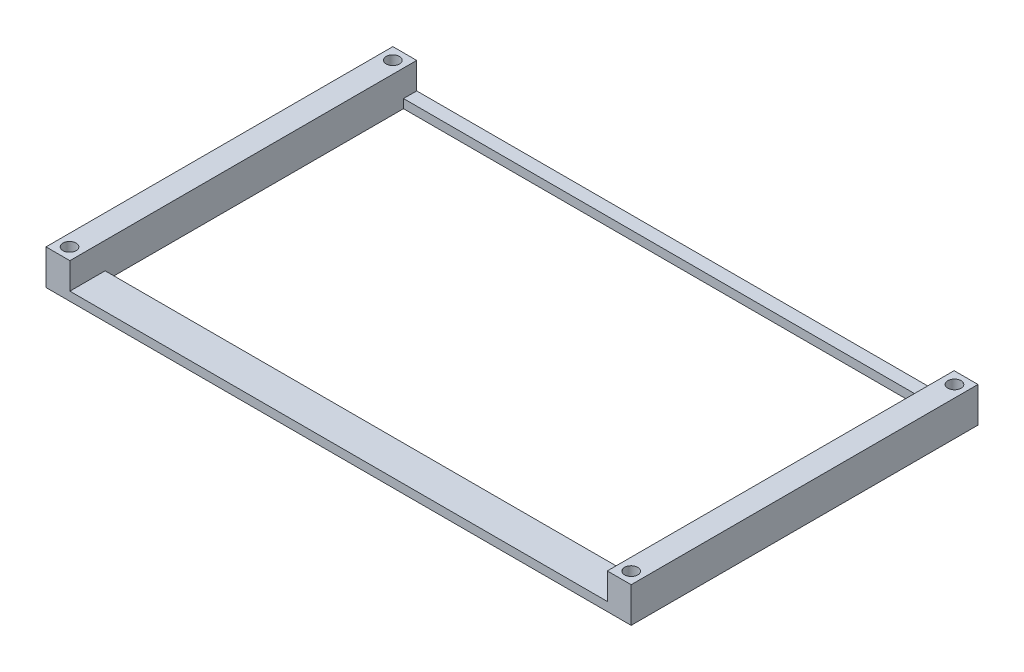
SolidWorks part; units mm, degrees
ref_plane "Front Plane" through (0, 0, 0) normal (0, 0, 1) x (1, 0, 0)
ref_plane "Top Plane" through (0, 0, 0) normal (0, 1, 0) x (1, 0, 0)
ref_plane "Right Plane" through (0, 0, 0) normal (1, 0, 0) x (0, 0, -1)
sketch "Sketch1" plane through (0, 0, 0) normal (0, 1, 0) x (1, 0, 0)
  line L0 (-66.42, -39.37) -> (66.42, -39.37)
  line L1 (-66.42, -39.37) -> (-66.42, 39.37)
  line L2 (-66.42, 39.37) -> (66.42, 39.37)
  line L3 (66.42, -39.37) -> (66.42, 39.37)
  line L4 (-66.42, -39.37) -> (66.42, 39.37) construction
  line L5 (-66.42, 39.37) -> (66.42, -39.37) construction
  line L6 (-66.42, 39.37) -> (-58.92, 31.87) construction
  line L7 (0, 39.37) -> (0, -39.37) construction
  line L8 (-66.42, 39.37) -> (-58.92, 39.37)
  line L9 (-66.42, 39.37) -> (-66.42, 31.87)
  line L12 (-66.42, 0) -> (66.42, 0) construction
  line L13 (-61, -31.37) -> (61, -31.37)
  line L14 (-61, -39.37) -> (61, -39.37)
  line L15 (-61, -39.37) -> (-61, 39.37)
  line L16 (-61, 39.37) -> (61, 39.37)
  line L17 (61, -39.37) -> (61, 39.37)
  line L18 (-61, 36.37) -> (61, 36.37)
  circle A0 centre (-63.75, 36.7) radius 1.5
  circle A4 centre (63.75, 36.7) radius 1.5
  circle A5 centre (-63.75, -36.7) radius 1.5
  circle A6 centre (63.75, -36.7) radius 1.5
  point P0 (0, 0)
  point P20 (0, -39.37)
  dimension "D1" = 3
  dimension "D2" = 7.5
  dimension "D3" = 78.74
  dimension "D4" = 132.84
  dimension "D5" = 2.67
  dimension "D6" = 45
  dimension "D7" = 7.5
  dimension "D8" = 122
  dimension "D9" = 8
  dimension "D10" = 3
extrude "Boss-Extrude1" add sketch "Sketch1" along normal blind 2 contours L0 L17 L13 L15 | L17 L0 L3 L2 A6 A4 | L15 L18 L17 L2 L8 | L0 L15 L2 L1 A0 A5 region at (-63.7086, 0, 0) region at (0, 0, 35.37) region at (63.7086, 0, 0) region at (0, 0, -37.87)
extrude "Boss-Extrude3" add sketch "Sketch1<5>" along normal blind 8 contours L0 L15 L2 L1 A0 A5 | L17 L0 L3 L2 A6 A4 region at (-63.7086, 0, 0) region at (63.7086, 0, 0)
sketch "Sketch1<5>" plane through (0, 0, 0) normal (0, 1, 0) x (1, 0, 0) same geometry as "Sketch1"
